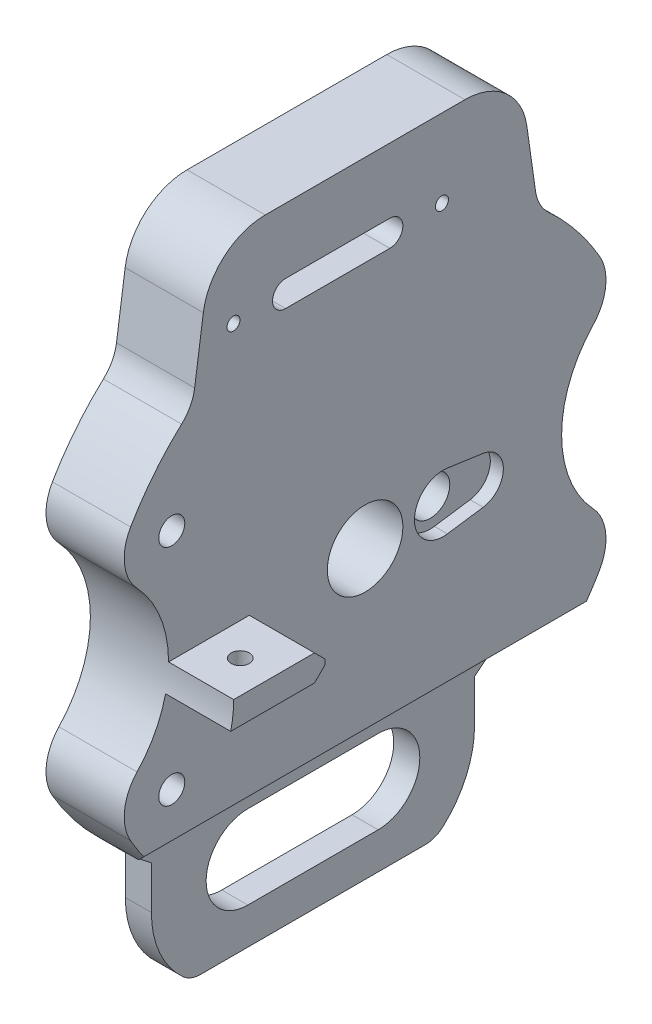
SolidWorks part; units mm, degrees
ref_plane "Płaszczyzna przednia" through (0, 0, 0) normal (0, 0, 1) x (1, 0, 0)
ref_plane "Płaszczyzna górna" through (0, 0, 0) normal (0, 1, 0) x (1, 0, 0)
ref_plane "Płaszczyzna prawa" through (0, 0, 0) normal (1, 0, 0) x (0, 0, -1)
sketch "Szkic1" plane through (0, 0, 0) normal (1, 0, 0) x (0, 0, -1)
  line L0 (-25, -100) -> (25, -100) construction
  line L1 (-25, -84) -> (25, -84)
  line L2 (-25, -116) -> (25, -116)
  line L3 (0, 0) -> (0, -130.3815) construction
  line L4 (0, 0) -> (-120, 0) construction
  line L5 (0, 0) -> (0, 195.8303) construction
  line L6 (0, 0) -> (-20.5826, 195.8303) construction
  line L7 (-30.5104, 100) -> (9.4896, 100) construction
  line L8 (-30.5104, 105) -> (9.4896, 105) construction
  line L9 (-30.5104, 95) -> (9.4896, 95) construction
  line L19 (62.0766, 109.386) -> (65.4007, 86.06)
  line L20 (38.3166, 130) -> (-38.3166, 130)
  line L21 (-62.0766, 109.386) -> (-65.4007, 86.06)
  line L28 (-25, -130) -> (25, -130)
  line L33 (-25, -70) -> (25, -70) construction
  line L35 (-25, -130) -> (-43.1384, -130)
  line L36 (62, -100) -> (62, -83.4985)
  line L38 (-62, -100) -> (-62, -83.4985)
  line L39 (25, -130) -> (43.1384, -130)
  line L40 (-62, -82.8995) -> (-69.9497, -74.9497) construction
  line L41 (69.9497, -74.9497) -> (62, -82.8995) construction
  line L42 (-25, -137) -> (25, -137) construction
  line L43 (65, -70) -> (55, -80) construction
  line L44 (55, -100) -> (55, -80) construction
  line L45 (-55, -80) -> (-65, -70) construction
  line L46 (-55, -100) -> (-55, -80) construction
  line L47 (-62, -100) -> (-62, -82.8995) construction
  line L48 (62, -100) -> (62, -82.8995) construction
  circle A0 centre (0, 0) radius 14.5
  arc A1 (-25, -84) -> (-25, -116) centre (-25, -100) ccw
  arc A2 (25, -116) -> (25, -84) centre (25, -100) ccw
  circle A3 centre (0, 0) radius 85.75 construction
  arc A4 (-30.5104, 105) -> (-30.5104, 95) centre (-30.5104, 100) ccw construction
  arc A5 (9.4896, 95) -> (9.4896, 105) centre (9.4896, 100) ccw construction
  circle A24 centre (-74.1894, 43) radius 5
  circle A25 centre (-74.1894, -43) radius 5
  arc A26 (-89.9789, -52.1516) -> (-62, -83.4985) centre (0, 0) ccw
  arc A32 (87.4958, -30.51) -> (89.9789, -52.1516) centre (74.1894, -43) cw
  arc A33 (87.4958, -30.51) -> (87.4958, 30.51) centre (120, 0) cw
  arc A34 (89.9789, 52.1516) -> (87.4958, 30.51) centre (74.1894, 43) cw
  arc A35 (70.4086, 76.5417) -> (89.9789, 52.1516) centre (0, 0) cw
  arc A36 (65.4007, 86.06) -> (70.4086, 76.5417) centre (81.2407, 88.3174) ccw
  arc A37 (38.3166, 130) -> (62.0766, 109.386) centre (38.3166, 106) cw
  arc A38 (-38.3166, 130) -> (-62.0766, 109.386) centre (-38.3166, 106) ccw
  arc A39 (-65.4007, 86.06) -> (-70.4086, 76.5417) centre (-81.2407, 88.3174) cw
  arc A40 (-70.4086, 76.5417) -> (-89.9789, 52.1516) centre (0, 0) ccw
  arc A41 (-89.9789, 52.1516) -> (-87.4958, 30.51) centre (-74.1894, 43) ccw
  arc A42 (-87.4958, -30.51) -> (-87.4958, 30.51) centre (-120, 0) ccw
  arc A43 (-87.4958, -30.51) -> (-89.9789, -52.1516) centre (-74.1894, -43) ccw
  arc A54 (89.9789, -52.1516) -> (62, -83.4985) centre (0, 0) cw
  arc A55 (49.8563, -127.4074) -> (62, -100) centre (25, -100) ccw
  arc A56 (-25, -70) -> (-25, -130) centre (-25, -100) ccw construction
  arc A57 (25, -130) -> (25, -70) centre (25, -100) ccw construction
  arc A58 (-62, -100) -> (-49.8563, -127.4074) centre (-25, -100) ccw
  arc A59 (49.8563, -127.4074) -> (43.1384, -130) centre (43.1384, -120) cw
  arc A60 (-62, -100) -> (-25, -137) centre (-25, -100) ccw construction
  arc A61 (25, -137) -> (62, -100) centre (25, -100) ccw construction
  arc A62 (25, -130) -> (55, -100) centre (25, -100) ccw construction
  arc A63 (-55, -100) -> (-25, -130) centre (-25, -100) ccw construction
  arc A64 (-43.1384, -130) -> (-49.8563, -127.4074) centre (-43.1384, -120) cw
  point P5 (0, -100)
  point P12 (-74.1894, -43)
  point P13 (-74.1894, 43)
  point P19 (-10.5104, 100)
  point P24 (-25, -70)
  point P25 (25, -70)
  point P30 (25, -100)
  point P33 (-25, -130)
  point P34 (-25, -100)
  point P43 (-25.5104, 81)
  point P52 (46.6564, -130)
  point P57 (-46.6564, -130)
  point P72 (0, 126)
  dimension "D1" = 29
  dimension "D3" = 16
  dimension "D5" = 86
  dimension "D7" = 171.5
  dimension "D9" = 40
  dimension "D10" = 5
  dimension "D18" = 120
  dimension "D13" = 7
  dimension "D14" = 10
  dimension "D2" = 50
  dimension "D4" = 100
  dimension "D6" = 43
  dimension "D8" = 6
  dimension "D11" = 100
  dimension "D12" = 14
extrude "Dodanie-wyciągnięcie1" add sketch "Szkic1" along normal mid plane 30
hole_wizard "M6 Tapped Hole1" positions "Sketch1" profile "Sketch2" tap size "M6" standard "ISO" end condition through all
sketch "Sketch1" plane through (15, 0, 0) normal (1, 0, 0) x (0, 0, -1)
  line L0 (-81.7008, 100) -> (63.4141, 100) construction
  line L2 (0, 0) -> (0, 150.2111) construction
  line L4 (65.4007, 86.06) -> (62.0766, 109.386) construction
  line L5 (38.3166, 130) -> (-38.3166, 130) construction
  line L7 (-10.5104, 105) -> (-10.5104, 95) construction
  line L8 (9.4896, 105) -> (-30.5104, 105) construction
  line L9 (-30.5104, 95) -> (9.4896, 95) construction
  point P0 (-50.5104, 100)
  point P2 (29.4896, 100)
  dimension "D1" = 40
  dimension "D2" = 40
  dimension "D3" = 30
sketch "Sketch2" plane through (15, 100, 50.5104) normal (0, 1, 0) x (0, 0, -1)
  line L0 (0, 0) -> (0, 30)
  line L1 (0, 30) -> (2.5, 30)
  line L2 (2.5, 30) -> (2.5, 0)
  line L5 (2.5, 0) -> (0, 0)
  line L11 (0, -6.35) -> (0, 107.95) construction
  dimension "Thru Tap Drill Dia." = 5
  dimension "Thru Tap Drill Depth" = 30
cosmetic thread "Hole Thread1" parameters "D2"=6
cosmetic thread "Hole Thread2" parameters "D2"=6
sketch "Szkic4" plane through (-15, 0, 0) normal (-1, 0, 0) x (0, 0, 1)
  line L0 (30.5104, 105) -> (-9.4896, 105) construction
  line L1 (30.5104, 105) -> (-9.4896, 105)
  line L2 (30.5104, 95) -> (-9.4896, 95) construction
  line L3 (30.5104, 95) -> (-9.4896, 95)
  arc A0 (30.5104, 95) -> (30.5104, 105) centre (30.5104, 100) ccw construction
  arc A1 (30.5104, 95) -> (30.5104, 105) centre (30.5104, 100) ccw
  arc A2 (-9.4896, 105) -> (-9.4896, 95) centre (-9.4896, 100) ccw construction
  arc A3 (-9.4896, 105) -> (-9.4896, 95) centre (-9.4896, 100) ccw
sketch "Szkic5" plane through (15, 0, 0) normal (-1, 0, 0) x (0, 0, 1)
  line L0 (0, 0) -> (75.42, 0) construction
  line L2 (75.42, 0) -> (44.42, 0)
  line L4 (76.556, -10) -> (44.42, -10)
  line L5 (40.42, -4) -> (40.42, -6)
  line L6 (44.42, 0) -> (40.42, -4)
  line L7 (40.42, -6) -> (44.42, -10)
  arc A0 (87.4958, 30.51) -> (87.4958, -30.51) centre (120, 0) ccw construction
  arc A1 (75.42, 0) -> (76.556, -10) centre (120, 0) ccw
  point P3 (40.42, -10)
  point P5 (40.42, 0)
  dimension "D1" = 10
  dimension "D2" = 35
extrude "Dodanie-wyciągnięcie3" add sketch "Szkic5" against normal blind 25 contours L2 L6 L5 L7 L4 A1
hole_wizard "Otwór gwintowany M8x1.01" positions "Szkic10" profile "Szkic11" tap size "M8x1.0" standard "ISO"
sketch "Szkic10" plane through (0, 0, 0) normal (0, 1, 0) x (1, 0, 0)
  line L2 (40, -75.42) -> (40, -44.42) construction
  line L3 (40, -75.42) -> (15, -75.42) construction
  point P8 (27.5, -60.42)
  dimension "D3" = 12.5
  dimension "D4" = 15
sketch "Szkic11" plane through (27.5, 0, 60.42) normal (1, 0, 0) x (0, 0, 1)
  line L0 (0, 0) -> (0, 21)
  line L1 (0, 21) -> (3.5, 18.897)
  line L2 (3.5, 18.897) -> (3.5, 0)
  line L5 (3.5, 0) -> (0, 0)
  line L10 (0, 21) -> (-3.5, 18.897) construction
  line L11 (0, -6.35) -> (0, 107.95) construction
  dimension "Średnica wiertła gwintu" = 7
  dimension "Głębokość otworu gwintowanego" = 21
  dimension "Kąt wiertła" = 118
sketch "Szkic12" plane through (15, 0, 0) normal (1, 0, 0) x (0, 0, -1)
  line L2 (9.4896, 105) -> (-30.5104, 105)
  line L3 (-30.5104, 95) -> (9.4896, 95)
  line L4 (9.4896, 105) -> (-30.5104, 105)
  line L5 (-30.5104, 95) -> (9.4896, 95)
  arc A2 (9.4896, 95) -> (9.4896, 105) centre (9.4896, 100) ccw
  arc A3 (-30.5104, 105) -> (-30.5104, 95) centre (-30.5104, 100) ccw
  arc A4 (9.4896, 95) -> (9.4896, 105) centre (9.4896, 100) ccw
  arc A5 (-30.5104, 105) -> (-30.5104, 95) centre (-30.5104, 100) ccw
  dimension "D1" = 0
extrude "Wytnij-wyciągnięcie2" cut sketch "Szkic12" against normal blind 10 contours A5 L5 A4 L4
sketch "Szkic16" plane through (15, 0, 0) normal (1, 0, 0) x (0, 0, -1)
  line L0 (-25, -116) -> (25, -116) construction
  line L1 (25, -84) -> (-25, -84) construction
  line L3 (-43.1384, -130) -> (43.1384, -130) construction
  line L5 (-25, -116) -> (25, -116)
  line L6 (25, -84) -> (-25, -84)
  line L7 (62, -100) -> (62, -83.4985) construction
  line L8 (-43.1384, -130) -> (43.1384, -130)
  line L9 (-62, -83.4985) -> (-62, -100) construction
  line L10 (-62, -100) -> (62, -100) construction
  line L11 (-76.9155, -70) -> (76.9155, -70)
  line L12 (62, -100) -> (62, -83.4985)
  line L13 (-62, -83.4985) -> (-62, -100)
  arc A0 (-25, -84) -> (-25, -116) centre (-25, -100) ccw construction
  arc A1 (25, -116) -> (25, -84) centre (25, -100) ccw construction
  arc A3 (43.1384, -130) -> (49.8563, -127.4074) centre (43.1384, -120) ccw construction
  arc A4 (-49.8563, -127.4074) -> (-43.1384, -130) centre (-43.1384, -120) ccw construction
  arc A6 (-25, -84) -> (-25, -116) centre (-25, -100) ccw
  arc A7 (25, -116) -> (25, -84) centre (25, -100) ccw
  arc A9 (43.1384, -130) -> (49.8563, -127.4074) centre (43.1384, -120) ccw
  arc A10 (-49.8563, -127.4074) -> (-43.1384, -130) centre (-43.1384, -120) ccw
  arc A14 (-89.9789, -52.1516) -> (-62, -83.4985) centre (0, 0) ccw construction
  arc A15 (-76.9155, -70) -> (-62, -83.4985) centre (0, 0) ccw
  arc A16 (62, -83.4985) -> (89.9789, -52.1516) centre (0, 0) ccw construction
  arc A17 (62, -83.4985) -> (76.9155, -70) centre (0, 0) ccw
  arc A18 (49.8563, -127.4074) -> (62, -100) centre (25, -100) ccw construction
  arc A19 (-62, -100) -> (-49.8563, -127.4074) centre (-25, -100) ccw construction
  arc A20 (49.8563, -127.4074) -> (62, -100) centre (25, -100) ccw
  arc A21 (-62, -100) -> (-49.8563, -127.4074) centre (-25, -100) ccw
extrude "Wytnij-wyciągnięcie4" cut sketch "Szkic16" against normal blind 20
chamfer "Sfazowanie4" distance 10 angle 45 1 edges at (15, -70, 0)
sketch "Szkic17" plane through (15, 0, 0) normal (1, 0, 0) x (0, 0, -1)
  line L4 (31.5786, -10.9367) -> (45.2929, -8.9572)
  line L5 (45.2929, 8.9572) -> (31.5786, 10.9367)
  arc A4 (31.5786, 10.9367) -> (18.9801, -0.8154) centre (30, 0) ccw
  arc A5 (18.9801, -0.8154) -> (31.5786, -10.9367) centre (30, 0) ccw
  circle A6 centre (30, 0) radius 7.5
  arc A11 (45.2929, -8.9572) -> (45.2929, 8.9572) centre (44, 0) ccw
  point P0 (8.9572, 38.7071)
  point P1 (-0.6678, 49.0253)
  point P3 (-8.9572, 38.7071)
  point P5 (-6.9777, 24.9929)
  point P6 (0, 26)
  point P7 (4.5988, 31.3435)
  point P8 (0, 26)
  point P9 (6.9777, 24.9929)
  point P21 (0, 26)
  point P22 (5.9035, 32.8594)
  dimension "D1" = 14
  dimension "D2" = 30
extrude "Wytnij-wyciągnięcie5" cut sketch "Szkic17" against normal blind 5 contours L4 A11 L5 A4 A5
extrude "Wytnij-wyciągnięcie6" cut sketch "Szkic17<5>" against normal through all contours A6
sketch "Szkic17<5>" plane through (15, 0, 0) normal (1, 0, 0) x (0, 0, -1) same geometry as "Szkic17"
